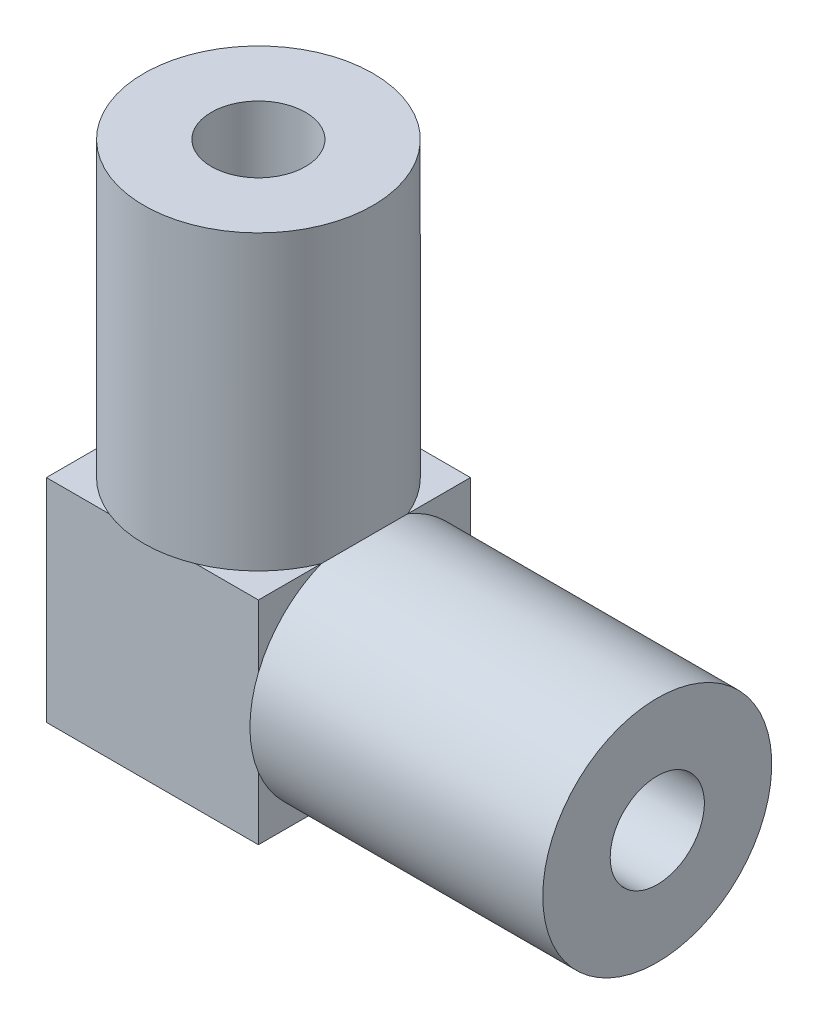
SolidWorks part; units mm, degrees
ref_plane "Front Plane" through (0, 0, 0) normal (0, 0, 1) x (1, 0, 0)
ref_plane "Top Plane" through (0, 0, 0) normal (0, 1, 0) x (1, 0, 0)
ref_plane "Right Plane" through (0, 0, 0) normal (1, 0, 0) x (0, 0, -1)
sketch "Block Sketch" plane through (0, 0, 0) normal (0, 0, 1) x (1, 0, 0)
  line L0 (-7.15, -7.15) -> (7.15, -7.15)
  line L1 (7.15, -7.15) -> (7.15, 7.15)
  line L2 (7.15, 7.15) -> (-7.15, 7.15)
  line L3 (-7.15, 7.15) -> (-7.15, -7.15)
extrude "Block" add sketch "Block Sketch" along normal mid plane 14.3
ref_axis "Engine Axis" through (28.6311, 0, 0) along (-1, 0, 0)
ref_axis "Stem Axis" through (0, -9.4531, 0) along (0, 1, 0)
sketch "Arm X Sketch" plane through (0, 0, 0) normal (0, 0, 1) x (1, 0, 0)
  line L0 (-1000, 0) -> (1000, 0) construction
  line L1 (7.15, 0) -> (26.9, 0)
  line L2 (26.9, 0) -> (26.9, 7.722)
  line L3 (26.9, 7.722) -> (7.15, 7.722)
  line L4 (7.15, 7.722) -> (7.15, 0)
revolve "Arm X" add sketch "Arm X Sketch" angle 360 about L0
sketch "Arm Y Sketch" plane through (0, 0, 0) normal (0, 0, 1) x (1, 0, 0)
  line L0 (0, -500) -> (0, 500) construction
  line L1 (0, 7.15) -> (7.722, 7.15)
  line L2 (7.722, 7.15) -> (7.722, 26.9)
  line L3 (7.722, 26.9) -> (0, 26.9)
  line L4 (0, 26.9) -> (0, 7.15)
revolve "Arm Y" add sketch "Arm Y Sketch" angle 360 about L0
sketch "Socket X Sketch" plane through (0, 0, 0) normal (0, 0, 1) x (1, 0, 0)
  line L0 (-1000, 0) -> (1000, 0) construction
  line L1 (11.7, 0) -> (27.9, 0)
  line L2 (27.9, 0) -> (27.9, 3.175)
  line L3 (27.9, 3.175) -> (11.7, 3.175)
  line L4 (11.7, 3.175) -> (11.7, 0)
revolve "Socket X" cut sketch "Socket X Sketch" angle 360 about L0
sketch "Socket Y Sketch" plane through (0, 0, 0) normal (0, 0, 1) x (1, 0, 0)
  line L0 (0, -500) -> (0, 500) construction
  line L1 (0, 11.7) -> (3.175, 11.7)
  line L2 (3.175, 11.7) -> (3.175, 27.9)
  line L3 (3.175, 27.9) -> (0, 27.9)
  line L4 (0, 27.9) -> (0, 11.7)
revolve "Socket Y" cut sketch "Socket Y Sketch" angle 360 about L0
